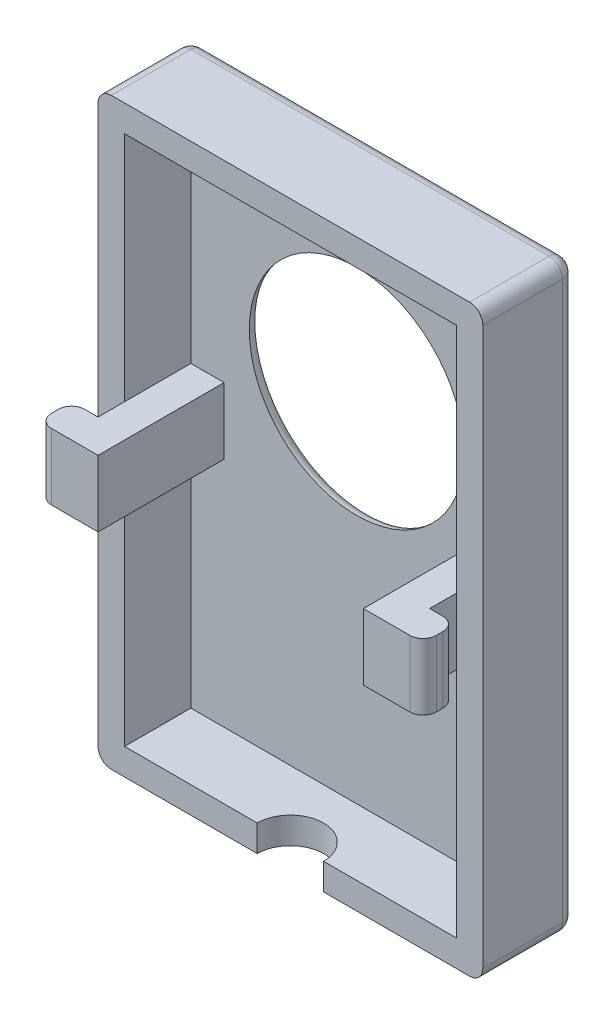
SolidWorks part; units mm, degrees
ref_plane "Front Plane" through (0, 0, 0) normal (0, 0, 1) x (1, 0, 0)
ref_plane "Top Plane" through (0, 0, 0) normal (0, 1, 0) x (1, 0, 0)
ref_plane "Right Plane" through (0, 0, 0) normal (1, 0, 0) x (0, 0, -1)
sketch "Sketch1" plane through (0, 0, 0) normal (0, 0, 1) x (1, 0, 0)
  line L1 (-14.5, 22) -> (14.5, 22)
  line L2 (-14.5, 22) -> (-14.5, -22)
  line L3 (-14.5, -22) -> (14.5, -22)
  line L4 (14.5, 22) -> (14.5, -22)
  line L5 (-14.5, 22) -> (14.5, -22) construction
  line L6 (-14.5, -22) -> (14.5, 22) construction
  point P0 (0, 0)
  dimension "D1" = 29
  dimension "D2" = 44
extrude "Boss-Extrude1" add sketch "Sketch1" along normal blind 2
sketch "Sketch2" plane through (0, 0, 2) normal (0, 0, 1) x (1, 0, 0)
  line L3 (-14.5, 22) -> (14.5, 22)
  line L4 (-14.5, 22) -> (-14.5, -22)
  line L5 (-12.5, 20) -> (-12.5, -20)
  line L9 (-14.5, -22) -> (14.5, -22)
  line L11 (12.5, 20) -> (12.5, -20)
  line L14 (12.5, -20) -> (-12.5, -20)
  line L15 (-12.5, -20) -> (-12.5, 20)
  line L16 (-12.5, 20) -> (12.5, 20)
  line L17 (14.5, 22) -> (14.5, -22)
  line L18 (-14.5, 22) -> (14.5, -22) construction
  line L19 (-14.5, -22) -> (14.5, 22) construction
  point P1 (0, 0)
  line M6 (14.5, -22) -> (14.5, 22)
  line M7 (14.5, 22) -> (-14.5, 22)
  line M8 (-14.5, 22) -> (-14.5, -22)
  line M9 (-14.5, -22) -> (14.5, -22)
  dimension "D1" = 2
  dimension "D2" = 2
extrude "Boss-Extrude2" add sketch "Sketch2" along normal blind 5 contours L5 L16 L11 L14 M9 M6 M7 M8 region at (0, 21.473, 2)
sketch "Sketch3" plane through (0, 0, 2) normal (0, 0, 1) x (1, 0, 0)
  circle A0 centre (0, 6.925) radius 8.1
  dimension "D2" = 16.2
extrude "Cut-Extrude1" cut sketch "Sketch3" against normal through all
sketch "Sketch4" plane through (0, -20, 0) normal (0, 1, 0) x (1, 0, 0)
  line L0 (14.5, -7) -> (-14.5, -7) construction
  line L1 (-2.5, -7) -> (2.5, -7)
  arc A0 (2.5, -7) -> (-2.5, -7) centre (0, -7) ccw
  dimension "D1" = 5
extrude "Cut-Extrude2" cut sketch "Sketch4" against normal through all
sketch "Sketch5" plane through (-12.5, 0, 0) normal (1, 0, 0) x (0, 0, -1)
  line L0 (-7, -2.5) -> (-2, -2.5)
  line L1 (-7, 20) -> (-7, -20) construction
  line L2 (-2, 20) -> (-2, -20) construction
  line L3 (-9, -2.5) -> (-7, -2.5)
  line L6 (-9, 2.5) -> (-11.5, 2.5)
  line L7 (-11.5, 0) -> (-11.5, 2.5)
  line L10 (-9, -2.5) -> (-11.5, -2.5)
  line L11 (-11.5, 0) -> (-11.5, -2.5)
  line L13 (-7, 2.5) -> (-9, 2.5)
  line L14 (-2, -2.5) -> (-2, 2.5)
  line L15 (-2, 2.5) -> (-7, 2.5)
  dimension "D2" = 2.5
  dimension "D3" = 2.5
  dimension "D4" = 2.5
extrude "Boss-Extrude3" add sketch "Sketch5" along normal blind 2.5
sketch "Sketch6" plane through (-12.5, 0, 0) normal (-1, 0, 0) x (0, 0, 1)
  line L1 (11.5, 2.5) -> (9, 2.5)
  line L2 (7, 2.5) -> (11.5, 2.5) construction
  line L3 (9, 2.5) -> (9, -2.5)
  line L4 (11.5, -2.5) -> (7, -2.5) construction
  line L5 (9, -2.5) -> (11.5, -2.5)
  line L6 (11.5, -2.5) -> (11.5, 2.5)
  dimension "D1" = 2.5
extrude "Boss-Extrude4" add sketch "Sketch6" along normal blind 2
sketch "Sketch7" plane through (12.5, 0, 0) normal (-1, 0, 0) x (0, 0, 1)
  line L3 (7, 2.5) -> (2, 2.5)
  line L4 (2, 0) -> (2, 2.5)
  line L5 (2, 20) -> (2, -20) construction
  line L9 (7, -2.5) -> (2, -2.5)
  line L10 (2, 0) -> (2, -2.5)
  line L11 (7, 2.5) -> (11.5, 2.5)
  line L13 (7, -2.5) -> (11.5, -2.5)
  line L14 (11.5, 2.5) -> (11.5, -2.5)
  dimension "D3" = 4.5
extrude "Boss-Extrude5" add sketch "Sketch7" along normal blind 2.5
sketch "Sketch8" plane through (12.5, 0, 0) normal (1, 0, 0) x (0, 0, -1)
  line L0 (-7, -2.5) -> (-11.5, -2.5) construction
  line L1 (-11.5, 2.5) -> (-9, 2.5)
  line L2 (-11.5, 2.5) -> (-11.5, -2.5)
  line L3 (-11.5, -2.5) -> (-9, -2.5)
  line L4 (-9, 2.5) -> (-9, -2.5)
  dimension "D1" = 2.5
extrude "Boss-Extrude6" add sketch "Sketch8" along normal blind 2
fillet "Fillet1" radius 1 4 edges at (-14.5, 0, 9) (-14.5, 0, 11.5) (14.5, 0, 11.5) (14.5, 0, 9)
sketch "Sketch9" plane through (0, 0, 0) normal (0, 0, -1) x (-1, 0, 0)
  line L1 (5.507, -2.6134) -> (11.014, 6.925)
  line L2 (11.014, 6.925) -> (5.507, 16.4634)
  line L3 (5.507, 16.4634) -> (-5.507, 16.4634)
  line L4 (-5.507, 16.4634) -> (-11.014, 6.925)
  line L5 (-11.014, 6.925) -> (-5.507, -2.6134)
  line L6 (-5.507, -2.6134) -> (5.507, -2.6134)
  circle A0 centre (0, 6.925) radius 8.1
  dimension "D1" = 16.2
extrude "Cut-Extrude3" cut sketch "Sketch9" against normal blind 1
fillet "Fillet2" radius 1 8 edges at (-14.5, -22, 3.5) (14.5, -22, 3.5) (14.5, 22, 3.5) (-14.5, 22, 3.5) (0, 22, 0) (14.5, 0, 0) (0, -22, 0) (-14.5, 0, 0)
sketch "Sketch10" plane through (0, 0, 0) normal (0, 0, -1) x (-1, 0, 0)
  text T0 "Meritus" font "Book Antiqua" height in points 8
extrude "Cut-Extrude4" cut sketch "Sketch10" against normal blind 1
fillet "Fillet3" radius 1 7 edges at (-8.2605, 2.1558, 0) (0, -2.6134, 0) (8.2605, 2.1558, 0) (8.2605, 11.6942, 0) (-8.2605, 11.6942, 0) (0, 16.4634, 0) (-8.1, 6.925, 1)
sketch "Sketch11" plane through (0, 0, 0) normal (0, 0, -1) x (-1, 0, 0)
  text T0 "Smoke detector" font "Centaur" height in points 8
extrude "Cut-Extrude5" cut sketch "Sketch11" against normal blind 1
